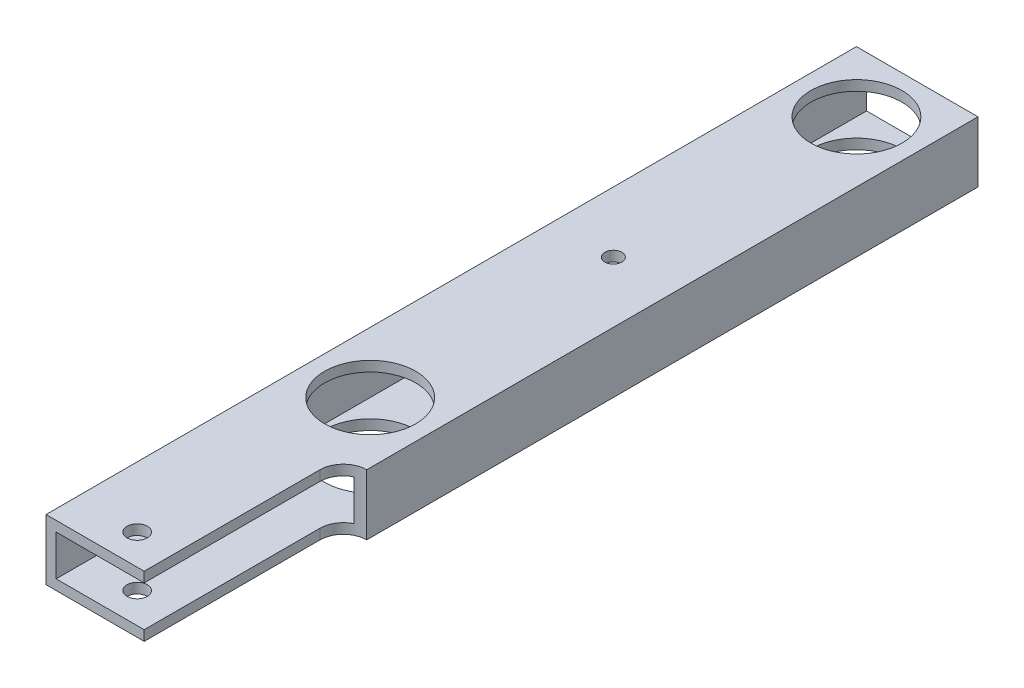
SolidWorks part; units mm, degrees
material "6063-T6"
ref_plane "Front" through (0, 0, 0) normal (0, 0, 1) x (1, 0, 0)
ref_plane "Top" through (0, 0, 0) normal (0, 1, 0) x (1, 0, 0)
ref_plane "Right" through (0, 0, 0) normal (1, 0, 0) x (0, 0, -1)
sketch "Sketch1" plane through (0, 0, 0) normal (0, 0, 1) x (1, 0, 0)
  line L0 (3.175, 3.175) -> (34.925, 3.175)
  line L1 (0, 0) -> (38.1, 0)
  line L2 (0, 0) -> (0, 19.05)
  line L3 (0, 19.05) -> (38.1, 19.05)
  line L4 (38.1, 0) -> (38.1, 19.05)
  line L5 (34.925, 3.175) -> (34.925, 15.875)
  line L6 (3.175, 15.875) -> (34.925, 15.875)
  line L7 (3.175, 3.175) -> (3.175, 15.875)
  dimension "D1" = 19.05
  dimension "D2" = 38.1
  dimension "D3" = 3.175
extrude "Boss-Extrude1" add sketch "Sketch1" along normal blind 254
sketch "Sketch2" plane through (0, 19.05, 0) normal (0, 1, 0) x (1, 0, 0)
  line L0 (19.05, 0) -> (19.05, -19.05) construction
  line L2 (19.05, -19.05) -> (19.05, -171.45) construction
  line L4 (38.1, -254) -> (38.1, 0) construction
  line L5 (38.1, 0) -> (0, 0) construction
  circle A0 centre (19.05, -19.05) radius 14.2875
  circle A1 centre (19.05, -171.45) radius 14.2875
  dimension "D1" = 28.575
  dimension "D4" = 28.575
  dimension "D2" = 19.05
  dimension "D3" = 152.4
  dimension "D5" = 19.05
extrude "Cut-Extrude1" cut sketch "Sketch2" against normal through all
sketch "Sketch3" plane through (0, 19.05, 0) normal (0, 1, 0) x (1, 0, 0)
  line L0 (19.05, -244.475) -> (19.05, -254) construction
  line L1 (38.1, -254) -> (0, -254) construction
  circle A0 centre (19.05, -244.475) radius 3.175
  dimension "D1" = 6.35
  dimension "D2" = 9.525
extrude "Cut-Extrude2" cut sketch "Sketch3" against normal through all
sketch "Sketch4" plane through (0, 19.05, 0) normal (0, 1, 0) x (1, 0, 0)
  line L0 (30.7745, -254) -> (30.7745, -198.9198)
  line L1 (38.1, -254) -> (0, -254) construction
  line L2 (38.1, -191.5943) -> (38.1, -254)
  line L3 (38.1, -254) -> (38.1, 0) construction
  line L4 (38.1, -254) -> (30.7745, -254)
  arc A0 (38.1, -191.5943) -> (30.7745, -198.9198) centre (38.1, -198.9198) ccw
extrude "Cut-Extrude3" cut sketch "Sketch4" against normal through all
sketch "Sketch5" plane through (0, 19.05, 0) normal (0, 1, 0) x (1, 0, 0)
  circle A0 centre (19.05, -95.25) radius 2.667 construction
  circle A1 centre (19.05, -95.25) radius 2.667
extrude "Cut-Extrude4" cut sketch "Sketch5" against normal through all
sketch "Sketch6" plane through (0, 0, 0) normal (0, -1, 0) x (1, 0, 0)
  circle A0 centre (19.05, 95.25) radius 6.35
  dimension "D1" = 12.7
extrude "Cut-Extrude5" cut sketch "Sketch6" against normal up to next
